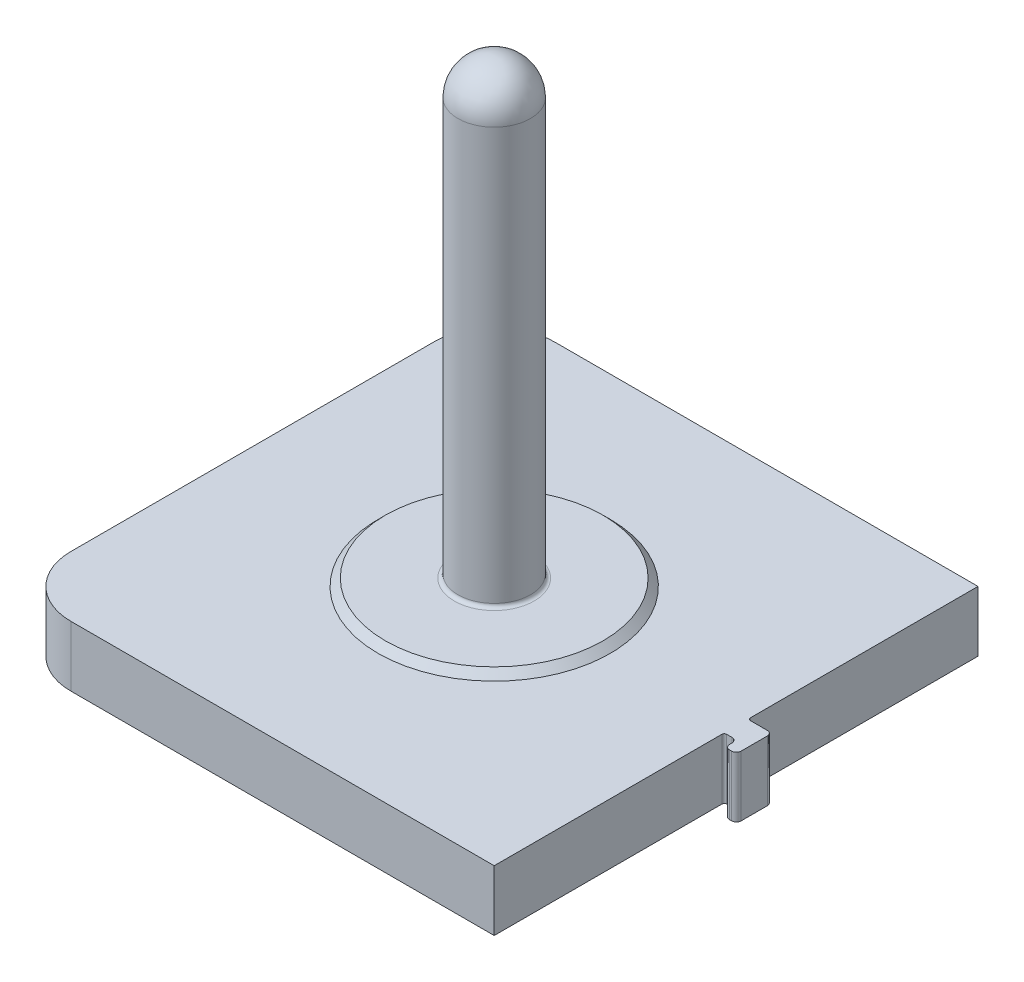
SolidWorks part; units mm, degrees
material "Custom Plastic"
ref_plane "Front Plane" through (0, 0, 0) normal (0, 0, 1) x (1, 0, 0)
ref_plane "Top Plane" through (0, 0, 0) normal (0, 1, 0) x (1, 0, 0)
ref_plane "Right Plane" through (0, 0, 0) normal (1, 0, 0) x (0, 0, -1)
sketch "Sketch1" plane through (0, 0, 0) normal (0, 1, 0) x (1, 0, 0)
  line L1 (100, -100) -> (-100, -100)
  line L2 (100, -100) -> (100, 100)
  line L3 (100, 100) -> (-100, 100)
  line L4 (-100, -100) -> (-100, 100)
  line L5 (100, -100) -> (-100, 100) construction
  line L6 (100, 100) -> (-100, -100) construction
  point P0 (0, 0)
  dimension "D1" = 200
  dimension "D2" = 200
extrude "Boss-Extrude1" add sketch "Sketch1" along normal blind 25
sketch "Sketch2" plane through (0, 25, 0) normal (0, 1, 0) x (1, 0, 0)
  circle A0 centre (0, 0) radius 15
  dimension "D1" = 30
extrude "Boss-Extrude2" add sketch "Sketch2" along normal blind 190
sketch "Sketch4" plane through (0, 0, 0) normal (0, 1, 0) x (1, 0, 0)
  line L0 (-1000, 0) -> (49000, 0) construction
  line L1 (100, -100) -> (100, 100) construction
  line L2 (100, -100) -> (100, 100) construction
  line L3 (100, 4.9) -> (108, 4.9)
  line L4 (110, 2.9) -> (110, -7.9)
  line L5 (108, -9.9) -> (107.2, -9.9)
  line L6 (105.2, -7.9) -> (105.2, -6.9)
  line L7 (103.2, -4.9) -> (100, -4.9)
  line L8 (100, -4.9) -> (100, 4.9)
  arc A0 (108, 4.9) -> (110, 2.9) centre (108, 2.9) cw
  arc A1 (110, -7.9) -> (108, -9.9) centre (108, -7.9) cw
  arc A2 (107.2, -9.9) -> (105.2, -7.9) centre (107.2, -7.9) cw
  arc A3 (105.2, -6.9) -> (103.2, -4.9) centre (103.2, -6.9) ccw
  point P7 (100, 0)
  point P15 (110, 4.9)
  point P18 (110, -9.9)
  point P21 (105.2, -9.9)
  point P24 (105.2, -4.9)
  dimension "D5" = 2
  dimension "D1" = 9.8
  dimension "D2" = 5.2
  dimension "D3" = 4.8
  dimension "D4" = 14.8
extrude "Boss-Extrude3" add sketch "Sketch4" along normal blind 25
fillet "Fillet1" radius 1 2 edges at (100, 12.5, -4.9) (100, 12.5, 4.9)
fillet "Fillet2" radius 25 2 edges at (-100, 12.5, -100) (-100, 12.5, 100)
fillet "Fillet3" radius 15 1 edges at (0, 215, 15)
sketch "Sketch5" plane through (0, 25, 0) normal (0, 1, 0) x (1, 0, 0)
  circle A0 centre (0, 0) radius 45
  dimension "D1" = 90
extrude "Boss-Extrude4" add sketch "Sketch5" along normal blind 3
chamfer "Chamfer1" distance 3 angle 45 1 edges at (0, 25, 45)
fillet "Fillet4" radius 1.5 1 edges at (0, 28, 15)
